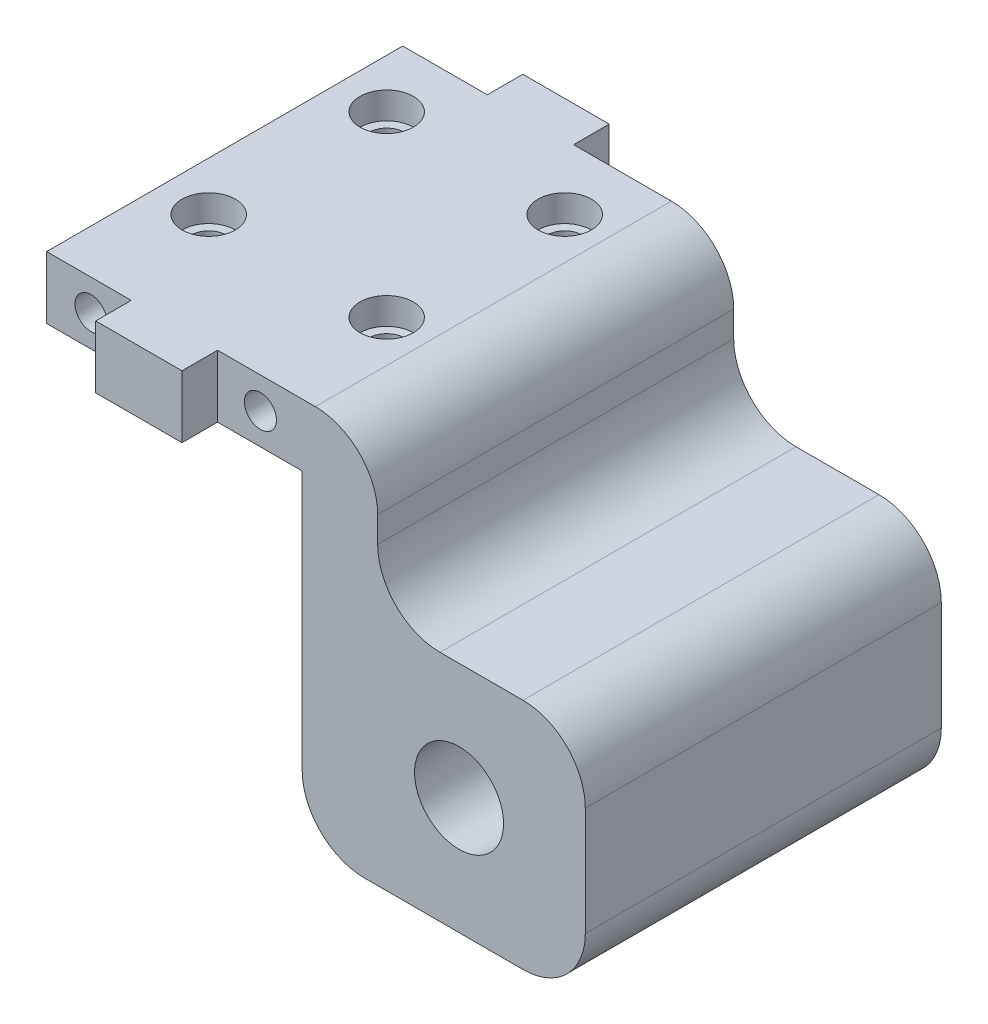
SolidWorks part; units mm, degrees
ref_plane "Front Plane" through (0, 0, 0) normal (0, 0, 1) x (1, 0, 0)
ref_plane "Top Plane" through (0, 0, 0) normal (0, 1, 0) x (1, 0, 0)
ref_plane "Right Plane" through (0, 0, 0) normal (1, 0, 0) x (0, 0, -1)
sketch "Sketch1" plane through (0, 0, 0) normal (0, 0, 1) x (1, 0, 0)
  line L2 (-10.8436, 3.5) -> (-10.8436, -3.5)
  line L3 (-10.8436, -3.5) -> (15.8563, -3.5)
  line L5 (24.3429, 3.5) -> (24.3429, -13.3983)
  line L6 (24.3429, -13.3983) -> (47.6667, -13.3983)
  line L9 (47.6667, -39.6017) -> (15.8563, -39.6017)
  line L10 (15.8563, -39.6017) -> (15.8563, -3.5)
  line L11 (-10.8436, 3.5) -> (24.3429, 3.5)
  line L12 (47.6667, -13.3983) -> (47.6667, -39.6017)
  line L13 (15.8563, -5.1) -> (15.8563, -12.9) construction
  line L14 (-10.2436, -3.5) -> (-3.7437, -3.5) construction
  line L15 (-10.8436, -8.7) -> (-10.8436, -4.1) construction
  point P1 (0, 0)
  point P7 (47.6667, -26.5)
  dimension "D1" = 7
extrude "Boss-Extrude1" add sketch "Sketch1" along normal blind 40
sketch "Sketch2" plane through (0, 0, 40) normal (0, 0, 1) x (1, 0, 0)
  circle A0 centre (33.484, -26.5) radius 10.8
  circle A1 centre (33.484, -26.5) radius 5
  dimension "D1" = 10
extrude "Cut-Extrude1" cut sketch "Sketch2" along normal blind 5 from surface contours A1 | A0 A1 region at (22.9895, -26.5, 40) region at (33.484, -26.5, 40) starting at face at (19.2556, -13.25, 0)
extrude "Cut-Extrude2" cut sketch "Sketch2<3>" against normal through all contours A1 region at (33.484, -26.5, 40)
sketch "Sketch2<3>" plane through (0, 0, 40) normal (0, 0, 1) x (1, 0, 0) same geometry as "Sketch2"
sketch "Sketch3" plane through (0, 0, 40) normal (0, 0, 1) x (1, 0, 0)
  circle A0 centre (33.6086, -34.499) radius 2
  circle A1 centre (25.485, -26.6246) radius 2
  circle A2 centre (33.3594, -18.501) radius 2
  circle A3 centre (41.483, -26.3754) radius 2
  dimension "D1" = 4
extrude "Cut-Extrude3" cut sketch "Sketch3" along normal blind 15 from surface starting at face at (22.684, -26.5, 0)
sketch "Sketch5" plane through (0, -3.5, 0) normal (0, -1, 0) x (1, 0, 0)
  circle A0 centre (-7.3436, 7.3) radius 2
  circle A1 centre (12.6564, 7.3) radius 2
  circle A3 centre (-7.3436, 27.3) radius 2
  circle A4 centre (12.6564, 27.3) radius 2
  dimension "D1" = 4
extrude "Cut-Extrude4" cut sketch "Sketch5" against normal through all
fillet "Fillet1" radius 7 5 edges at (47.6667, -39.6017, 20) (15.8563, -39.6017, 20) (24.3429, 3.5, 20) (24.3429, -13.3983, 20) (47.6667, -13.3983, 20)
sketch "Sketch12" plane through (0, 0, 0) normal (0, 0, -1) x (-1, 0, 0)
  circle A0 centre (-11.17, 0) radius 1.75
  circle A1 centre (7.8617, 0) radius 1.75
  dimension "D1" = 3.5
extrude "Cut-Extrude11" cut sketch "Sketch12" against normal blind 4
sketch "Sketch14" plane through (0, 3.5, 0) normal (0, 1, 0) x (1, 0, 0)
  circle A0 centre (-7.3436, -7.3) radius 3
  circle A1 centre (-7.3436, -27.3) radius 3
  circle A2 centre (12.6564, -27.3) radius 3
  circle A3 centre (12.6564, -7.3) radius 3
  dimension "D1" = 6
extrude "Cut-Extrude12" cut sketch "Sketch14" against normal blind 3
sketch "Sketch15" plane through (0, 0, 40) normal (0, 0, 1) x (1, 0, 0)
  circle A0 centre (-7.8617, 0) radius 1.8
  circle A1 centre (11.17, 0) radius 1.8
  dimension "D1" = 3.6
extrude "Cut-Extrude13" cut sketch "Sketch15" against normal blind 9
sketch "Sketch16" plane through (-10.8436, 0, 0) normal (-1, 0, 0) x (0, 0, 1)
  line L4 (0, 3.5) -> (0, -3.5)
  line L5 (0, -3.5) -> (40, -3.5)
  line L6 (40, -3.5) -> (40, 3.5)
  line L7 (40, 3.5) -> (0, 3.5)
  line L8 (0, 3.5) -> (0, -3.5)
  line L9 (0, -3.5) -> (40, -3.5)
  line L10 (40, -3.5) -> (40, 3.5)
  line L11 (40, 3.5) -> (0, 3.5)
  dimension "D1" = 0
extrude "Boss-Extrude5" add sketch "Sketch16" along normal blind 2
sketch "Sketch18" plane through (0, 0, 0) normal (0, 0, -1) x (-1, 0, 0)
  line L0 (-17.3429, 3.5) -> (12.8436, 3.5) construction
  line L1 (-6.3564, 3.5) -> (3.3436, 3.5)
  line L2 (-6.3564, 3.5) -> (-6.3564, -3.5)
  line L3 (-6.3564, -3.5) -> (3.3436, -3.5)
  line L4 (3.3436, 3.5) -> (3.3436, -3.5)
  line L5 (12.8436, -3.5) -> (-15.8563, -3.5) construction
  point P12 (-1.5064, -3.5)
  point P13 (-1.5064, -3.5)
  dimension "D1" = 9.7
  dimension "D2" = 0
extrude "Boss-Extrude6" add sketch "Sketch18" along normal blind 4
ref_plane "Plane2" through (0, 0, 20) normal (0, 0, -1) x (-1, 0, 0)
mirror "Mirror6" about plane through (0, 0, 20) normal (0, 0, -1) of "Boss-Extrude6"
